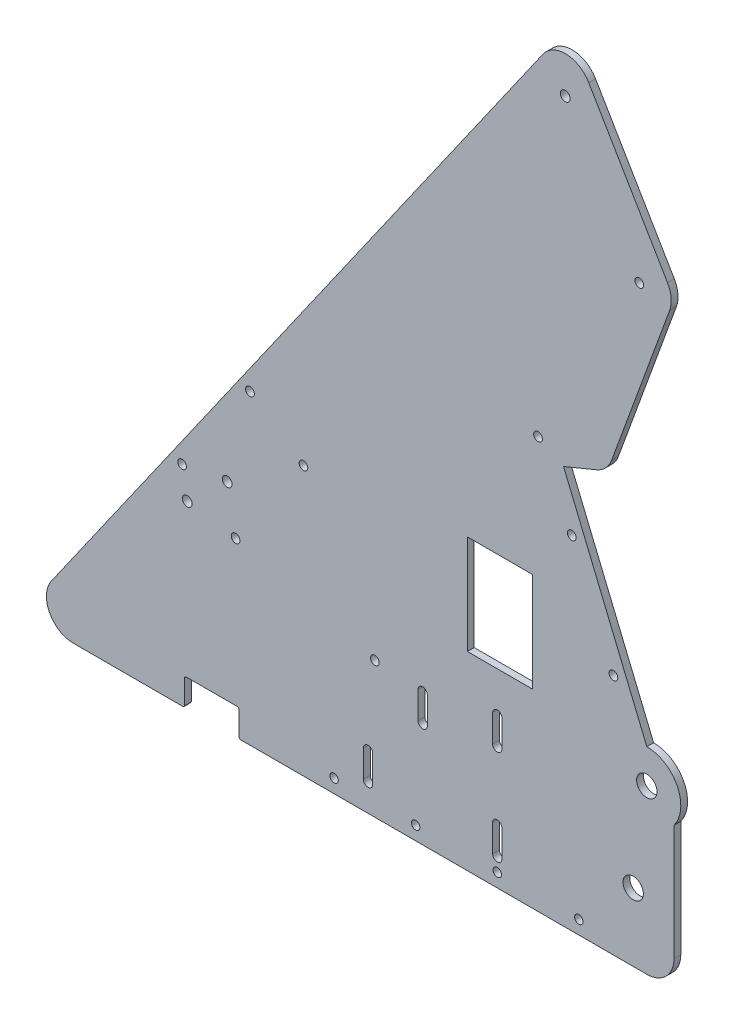
SolidWorks part; units mm, degrees
other "Markup1"
sketch "Sketch5"
ref_plane "Front Plane" through (0, 0, 0) normal (0, 0, 1) x (1, 0, 0)
ref_plane "Top Plane" through (0, 0, 0) normal (0, 1, 0) x (1, 0, 0)
ref_plane "Right Plane" through (0, 0, 0) normal (1, 0, 0) x (0, 0, -1)
sketch "Sketch1" plane through (0, 0, 0) normal (0, 0, 1) x (1, 0, 0)
  line L0 (0, 0) -> (76.2, 0)
  line L1 (304.8, 0) -> (304.8, 66.675)
  line L2 (254.9547, 364.1131) -> (0, 0)
  line L3 (304.8, 279.4) -> (254.9547, 364.1131)
  line L4 (76.2, 0) -> (76.2, 12.7)
  line L5 (76.2, 12.7) -> (101.6, 12.7)
  line L6 (101.6, 12.7) -> (101.6, 0)
  line L7 (101.6, 0) -> (304.8, 0)
  line L9 (292.1, 92.075) -> (253.2194, 185.9412)
  line L10 (253.2194, 185.9412) -> (273.7526, 194.4463)
  line L11 (273.7526, 194.4463) -> (304.8, 279.4)
  arc A0 (304.8, 66.675) -> (292.1, 92.075) centre (292.1, 76.2) ccw
  dimension "D7" = 12.7
  dimension "D8" = 76.2
  dimension "D10" = 31.75
  dimension "D1" = 304.8
  dimension "D2" = 279.4
  dimension "D3" = 55
  dimension "D4" = 444.5
  dimension "D5" = 76.2
  dimension "D6" = 25.4
  dimension "D9" = 292.1
  dimension "D11" = 101.6
  dimension "D12" = 22.5
  dimension "D13" = 22.225
extrude "Boss-Extrude1" add sketch "Sketch1" along normal blind 3.175
sketch "Sketch2" plane through (0, 0, 3.175) normal (0, 0, 1) x (1, 0, 0)
  line L0 (254.9547, 364.1131) -> (0, 0) construction
  line L1 (101.6, 0) -> (304.8, 0) construction
  line L2 (292.1, 92.075) -> (253.2194, 185.9412) construction
  line L3 (253.2194, 185.9412) -> (273.7526, 194.4463) construction
  line L4 (292.1, 92.075) -> (253.2194, 185.9412) construction
  line L5 (304.8, 279.4) -> (288.6002, 277.9261) construction
  line L6 (285.4785, 312.2373) -> (291.7219, 243.6149) construction
  line L7 (304.8, 279.4) -> (254.9547, 364.1131) construction
  line L8 (273.7526, 194.4463) -> (304.8, 279.4) construction
  line L9 (273.7526, 194.4463) -> (304.8, 279.4) construction
  circle A0 centre (77.4583, 84.0518) radius 2.286
  circle A1 centre (254, 336.1795) radius 2.286
  circle A2 centre (96.1158, 101.2872) radius 2.286
  circle A3 centre (257.0729, 160.0446) radius 2.032
  circle A4 centre (292.1, 76.2) radius 4.7625
  circle A5 centre (184.15, 6.35) radius 1.9682
  circle A6 centre (222.25, 6.35) radius 1.9682
  circle A7 centre (260.35, 6.35) radius 1.9682
  circle A8 centre (276.5132, 113.1115) radius 2.032
  circle A18 centre (288.6002, 277.9261) radius 2.032
  circle A26 centre (285.75, 31.75) radius 4.7625
  circle A28 centre (106.7599, 143.0587) radius 2.032
  circle A29 centre (106.7599, 143.0587) radius 2.032
  arc A30 (304.8, 66.675) -> (292.1, 92.075) centre (292.1, 76.2) ccw construction
  circle A31 centre (241.3, 192.0875) radius 2.032
  circle A34 centre (75.0727, 97.8047) radius 2.032
  circle A35 centre (75.0727, 97.8047) radius 2.032
  circle A37 centre (100.0405, 80.3221) radius 2.032
  circle A38 centre (100.0405, 80.3221) radius 2.032
  circle A39 centre (131.7277, 125.5761) radius 2.032
  circle A40 centre (131.7277, 125.5761) radius 2.032
  circle A41 centre (146.05, 6.35) radius 1.9682
  point P60 (288.6002, 277.9261)
  dimension "D3" = 4.572
  dimension "D5" = 4.572
  dimension "D9" = 4.572
  dimension "D14" = 3.9364
  dimension "D20" = 9.525
  dimension "D23" = 9.525
  dimension "D18" = 4.064
  dimension "D26" = 4.064
  dimension "D2" = 15.24
  dimension "D4" = 254
  dimension "D6" = 15.24
  dimension "D7" = 25.4
  dimension "D8" = 20.6375
  dimension "D15" = 146.05
  dimension "D16" = 6.35
  dimension "D21" = 44.45
  dimension "D22" = 6.35
  dimension "D19" = 160.3375
  dimension "D24" = 44.45
  dimension "D25" = 6.35
  dimension "D27" = 25.4
  dimension "D28" = 50.8
  dimension "D29" = 6.35
  dimension "D30" = 38.1
  dimension "D31" = 38.1
  dimension "D32" = 114.3
  dimension "D10" = 0.127
  dimension "D12" = 0.127
  dimension "D13" = 0.127
  dimension "D11" = 0.127
  dimension "D17" = 4
extrude "Cut-Extrude1" cut sketch "Sketch2" against normal through all
sketch "Sketch7" plane through (0, 0, 3.175) normal (0, 0, 1) x (1, 0, 0)
  line L0 (222.25, 12.7) -> (222.25, 25.4) construction
  line L1 (220.091, 12.7) -> (220.091, 25.4)
  line L2 (224.409, 12.7) -> (224.409, 25.4)
  line L3 (222.25, 57.15) -> (222.25, 69.85) construction
  line L4 (220.091, 57.15) -> (220.091, 69.85)
  line L5 (224.409, 57.15) -> (224.409, 69.85)
  line L6 (161.925, 12.7) -> (161.925, 25.4) construction
  line L9 (187.4205, 49.1113) -> (187.4205, 61.8113) construction
  line L10 (185.2615, 49.1113) -> (185.2615, 61.8113)
  line L11 (189.5795, 49.1113) -> (189.5795, 61.8113)
  line L12 (304.8, 0) -> (304.8, 66.675) construction
  line L13 (101.6, 0) -> (304.8, 0) construction
  line L14 (159.766, 12.7) -> (159.766, 25.4)
  line L15 (164.084, 12.7) -> (164.084, 25.4)
  line L16 (161.925, 25.4) -> (187.4205, 61.8113) construction
  line L17 (179.982, 60.9194) -> (167.4106, 42.9656) construction
  arc A0 (220.091, 12.7) -> (224.409, 12.7) centre (222.25, 12.7) ccw
  arc A1 (224.409, 25.4) -> (220.091, 25.4) centre (222.25, 25.4) ccw
  arc A2 (220.091, 57.15) -> (224.409, 57.15) centre (222.25, 57.15) ccw
  arc A3 (224.409, 69.85) -> (220.091, 69.85) centre (222.25, 69.85) ccw
  arc A6 (185.2615, 49.1113) -> (189.5795, 49.1113) centre (187.4205, 49.1113) ccw
  arc A7 (189.5795, 61.8113) -> (185.2615, 61.8113) centre (187.4205, 61.8113) ccw
  arc A13 (159.766, 12.7) -> (164.084, 12.7) centre (161.925, 12.7) ccw
  arc A14 (164.084, 25.4) -> (159.766, 25.4) centre (161.925, 25.4) ccw
  point P2 (222.25, 19.05)
  point P9 (222.25, 63.5)
  point P16 (161.925, 19.05)
  point P21 (187.4205, 55.4613)
  dimension "D1" = 4.318
  dimension "D2" = 12.7
  dimension "D3" = 12.7
  dimension "D4" = 44.45
  dimension "D5" = 44.45
  dimension "D7" = 82.55
  dimension "D8" = 12.7
  dimension "D9" = 60.325
extrude "Cut-Extrude2" cut sketch "Sketch7" against normal through all
sketch "Sketch10" plane through (0, 0, 3.175) normal (0, 0, 1) x (1, 0, 0)
  circle A0 centre (165.1, 63.5) radius 2.032
  point P2 (0, 0)
  point P6 (157.6665, 51.9379)
  dimension "D1" = 4.064
  dimension "D2" = 165.1
  dimension "D3" = 63.5
extrude "Cut-Extrude3" cut sketch "Sketch10" against normal up to next
fillet "Fillet1" radius 12.7 5 edges at (0, 0, 1.5875) (304.8, 0, 1.5875) (254.9547, 364.1131, 1.5875) (273.7526, 194.4463, 1.5875) (304.8, 279.4, 1.5875)
fillet "Fillet2" radius 0.7937 4 edges at (101.6, 0, 1.5875) (101.6, 12.7, 1.5875) (76.2, 0, 1.5875) (76.2, 12.7, 1.5875)
sketch "Sketch11" plane through (0, 0, 3.175) normal (0, 0, 1) x (1, 0, 0)
  line L1 (238.78, 88.6681) -> (208.3, 88.6681)
  line L2 (238.78, 88.6681) -> (238.78, 135.0231)
  line L3 (238.78, 135.0231) -> (208.3, 135.0231)
  line L4 (208.3, 88.6681) -> (208.3, 135.0231)
  point P4 (208.3, 135.0231)
  dimension "D1" = 46.355
  dimension "D2" = 30.48
extrude "Cut-Extrude4" cut sketch "Sketch11" against normal up to next
equation "\"D6@Sketch2\"=\"D2@Sketch2\""
